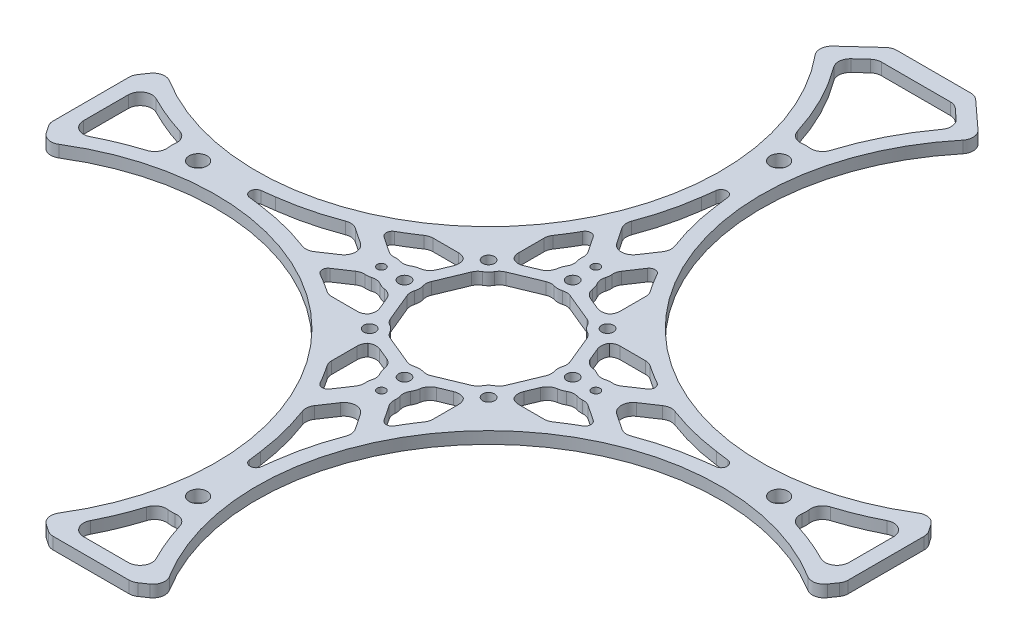
SolidWorks part; units mm, degrees
ref_plane "前视基准面" through (0, 0, 0) normal (0, 0, 1) x (1, 0, 0)
ref_plane "上视基准面" through (0, 0, 0) normal (0, 1, 0) x (1, 0, 0)
ref_plane "右视基准面" through (0, 0, 0) normal (1, 0, 0) x (0, 0, -1)
sketch "草图1" plane through (0, 0, 0) normal (0, 1, 0) x (1, 0, 0)
  line L113 (46.853, 0) -> (37.0698, -1.2734)
  line L116 (0, 46.853) -> (1.2734, 37.0698)
  line L147 (66.853, -7) -> (64.5647, -10.3188)
  line L164 (1.2737, 11.9909) -> (7.5782, 9.3795)
  line L244 (-0.0001, 20.7284) -> (4.0117, 26.7237)
  line L245 (5.4809, 23.5246) -> (2.3589, 18.8592)
  line L246 (7.4585, 11.5939) -> (2.9242, 13.4721)
  line L247 (8.5216, 12.6104) -> (8.5216, 18.495)
  line L253 (11.9909, -1.2737) -> (9.3795, -7.5782)
  line L254 (20.7284, 0.0001) -> (26.7237, -4.0117)
  line L257 (-8.5216, 12.6104) -> (-8.5216, 18.495)
  line L258 (-7.4585, 11.5939) -> (-2.9242, 13.4721)
  line L259 (-5.4809, 23.5246) -> (-2.3589, 18.8592)
  line L260 (0.0001, 20.7284) -> (-4.0117, 26.7237)
  line L262 (-1.2737, 11.9909) -> (-7.5782, 9.3795)
  line L266 (0, 46.853) -> (-1.2734, 37.0698)
  line L267 (23.5246, -5.4809) -> (18.8592, -2.3589)
  line L268 (11.5939, -7.4585) -> (13.4721, -2.9242)
  line L269 (12.6104, -8.5216) -> (18.495, -8.5216)
  line L272 (64.353, 7.1919) -> (64.353, -7.1919)
  line L273 (12.6104, 8.5216) -> (18.495, 8.5216)
  line L274 (11.5939, 7.4585) -> (13.4721, 2.9242)
  line L275 (23.5246, 5.4809) -> (18.8592, 2.3589)
  line L276 (20.7284, -0.0001) -> (26.7237, 4.0117)
  line L277 (11.9909, 1.2737) -> (9.3795, 7.5782)
  line L278 (66.853, 7) -> (64.5647, 10.3188)
  line L279 (66.853, -7) -> (66.853, 7)
  line L280 (46.853, 0) -> (37.0698, 1.2734)
  line L281 (0, -46.853) -> (-1.2734, -37.0698)
  line L282 (7, -66.853) -> (-7, -66.853)
  line L283 (-7, -66.853) -> (-10.3188, -64.5647)
  line L284 (-1.2737, -11.9909) -> (-7.5782, -9.3795)
  line L285 (0.0001, -20.7284) -> (-4.0117, -26.7237)
  line L286 (-5.4809, -23.5246) -> (-2.3589, -18.8592)
  line L287 (-7.4585, -11.5939) -> (-2.9242, -13.4721)
  line L288 (-8.5216, -12.6104) -> (-8.5216, -18.495)
  line L289 (-7.1919, -64.353) -> (7.1919, -64.353)
  line L290 (8.5216, -12.6104) -> (8.5216, -18.495)
  line L291 (7.4585, -11.5939) -> (2.9242, -13.4721)
  line L292 (5.4809, -23.5246) -> (2.3589, -18.8592)
  line L293 (-46.853, 0) -> (-37.0698, 1.2734)
  line L294 (-66.853, 7) -> (-64.5647, 10.3188)
  line L295 (-11.9909, 1.2737) -> (-9.3795, 7.5782)
  line L296 (-20.7284, -0.0001) -> (-26.7237, 4.0117)
  line L297 (-23.5246, 5.4809) -> (-18.8592, 2.3589)
  line L298 (-11.5939, 7.4585) -> (-13.4721, 2.9242)
  line L299 (-12.6104, 8.5216) -> (-18.495, 8.5216)
  line L300 (-0.0001, -20.7284) -> (4.0117, -26.7237)
  line L301 (1.2737, -11.9909) -> (7.5782, -9.3795)
  line L302 (-64.353, -7.1919) -> (-64.353, 7.1919)
  line L303 (-12.6104, -8.5216) -> (-18.495, -8.5216)
  line L304 (-11.5939, -7.4585) -> (-13.4721, -2.9242)
  line L305 (-23.5246, -5.4809) -> (-18.8592, -2.3589)
  line L306 (-20.7284, 0.0001) -> (-26.7237, -4.0117)
  line L307 (-11.9909, -1.2737) -> (-9.3795, -7.5782)
  line L308 (7, -66.853) -> (10.3188, -64.5647)
  line L309 (-66.853, -7) -> (-64.5647, -10.3188)
  line L310 (-66.853, 7) -> (-66.853, -7)
  line L311 (-46.853, 0) -> (-37.0698, -1.2734)
  line L312 (0, -46.853) -> (1.2734, -37.0698)
  line L314 (-7, 74.853) -> (7, 74.853)
  line L318 (7, 74.853) -> (13.6583, 68.7585)
  line L319 (0, -77.9383) -> (0, 77.9383) construction
  line L320 (-10.1817, 68.5516) -> (-6.5748, 71.853)
  line L322 (6.5748, 71.853) -> (-6.5748, 71.853)
  line L323 (10.1817, 68.5516) -> (6.5748, 71.853)
  line L324 (-7, 74.853) -> (-13.6583, 68.7585)
  circle A77 centre (0, 48.853) radius 1.5
  circle A138 centre (10, 10) radius 1
  circle A139 centre (0, 14.1421) radius 1
  circle A140 centre (0, 18.0312) radius 0.7
  arc A141 (-1.2737, 11.9909) -> (1.2737, 11.9909) centre (0, 14.1421) ccw
  arc A144 (7.5782, 9.3795) -> (9.3795, 7.5782) centre (10, 10) ccw
  arc A231 (4.0117, 26.7237) -> (1.2734, 37.0698) centre (42.4263, 42.4264) cw
  arc A232 (1.9284, 16.4402) -> (2.3589, 18.8592) centre (0, 18.0312) ccw
  arc A233 (2.9242, 13.4721) -> (1.9284, 16.4402) centre (0, 14.1421) ccw
  arc A234 (8.5216, 12.6104) -> (7.4585, 11.5939) centre (10, 10) ccw
  arc A235 (8.5216, 18.495) -> (5.4809, 23.5246) centre (42.4264, 42.4264) cw
  arc A236 (2.2334, 52.7597) -> (-2.2334, 52.7597) centre (0, 48.853) ccw
  arc A241 (-8.5216, 18.495) -> (-5.4809, 23.5246) centre (-42.4264, 42.4264) ccw
  arc A242 (-8.5216, 12.6104) -> (-7.4585, 11.5939) centre (-10, 10) cw
  arc A243 (-2.9242, 13.4721) -> (-1.9284, 16.4402) centre (0, 14.1421) cw
  arc A244 (-1.9284, 16.4402) -> (-2.3589, 18.8592) centre (0, 18.0312) cw
  arc A245 (-4.0117, 26.7237) -> (-1.2734, 37.0698) centre (-42.4263, 42.4264) ccw
  arc A246 (-7.5782, 9.3795) -> (-9.3795, 7.5782) centre (-10, 10) cw
  circle A247 centre (-10, 10) radius 1
  arc A249 (10.3188, -64.5647) -> (64.5647, -10.3188) centre (42.4264, -42.4264) cw
  circle A250 centre (10, -10) radius 1
  arc A251 (9.3795, -7.5782) -> (7.5782, -9.3795) centre (10, -10) ccw
  arc A252 (26.7237, -4.0117) -> (37.0698, -1.2734) centre (42.4264, -42.4263) cw
  arc A253 (16.4402, -1.9284) -> (18.8592, -2.3589) centre (18.0312, 0) ccw
  arc A254 (13.4721, -2.9242) -> (16.4402, -1.9284) centre (14.1421, 0) ccw
  arc A255 (12.6104, -8.5216) -> (11.5939, -7.4585) centre (10, -10) ccw
  arc A256 (18.495, -8.5216) -> (23.5246, -5.4809) centre (42.4264, -42.4264) cw
  arc A257 (52.7597, -2.2334) -> (64.353, -7.1919) centre (42.4264, -42.4264) cw
  arc A258 (52.7597, 2.2334) -> (64.353, 7.1919) centre (42.4264, 42.4264) ccw
  arc A259 (52.7597, 2.2334) -> (52.7597, -2.2334) centre (48.853, 0) cw
  arc A260 (18.495, 8.5216) -> (23.5246, 5.4809) centre (42.4264, 42.4264) ccw
  arc A261 (12.6104, 8.5216) -> (11.5939, 7.4585) centre (10, 10) cw
  arc A262 (13.4721, 2.9242) -> (16.4402, 1.9284) centre (14.1421, 0) cw
  arc A263 (16.4402, 1.9284) -> (18.8592, 2.3589) centre (18.0312, 0) cw
  arc A264 (26.7237, 4.0117) -> (37.0698, 1.2734) centre (42.4264, 42.4263) ccw
  arc A265 (11.9909, -1.2737) -> (11.9909, 1.2737) centre (14.1421, 0) cw
  circle A266 centre (18.0312, 0) radius 0.7
  circle A267 centre (14.1421, 0) radius 1
  circle A268 centre (48.853, 0) radius 1.5
  circle A269 centre (0, -48.853) radius 1.5
  circle A270 centre (0, -14.1421) radius 1
  circle A271 centre (0, -18.0312) radius 0.7
  arc A272 (1.2737, -11.9909) -> (-1.2737, -11.9909) centre (0, -14.1421) ccw
  arc A273 (-4.0117, -26.7237) -> (-1.2734, -37.0698) centre (-42.4263, -42.4264) cw
  arc A274 (-1.9284, -16.4402) -> (-2.3589, -18.8592) centre (0, -18.0312) ccw
  arc A275 (-2.9242, -13.4721) -> (-1.9284, -16.4402) centre (0, -14.1421) ccw
  arc A276 (-8.5216, -12.6104) -> (-7.4585, -11.5939) centre (-10, -10) ccw
  arc A277 (-8.5216, -18.495) -> (-5.4809, -23.5246) centre (-42.4264, -42.4264) cw
  arc A278 (-2.2334, -52.7597) -> (2.2334, -52.7597) centre (0, -48.853) ccw
  arc A279 (-2.2334, -52.7597) -> (-7.1919, -64.353) centre (-42.4264, -42.4264) cw
  arc A280 (2.2334, -52.7597) -> (7.1919, -64.353) centre (42.4264, -42.4264) ccw
  arc A281 (8.5216, -18.495) -> (5.4809, -23.5246) centre (42.4264, -42.4264) ccw
  arc A282 (8.5216, -12.6104) -> (7.4585, -11.5939) centre (10, -10) cw
  arc A283 (2.9242, -13.4721) -> (1.9284, -16.4402) centre (0, -14.1421) cw
  arc A284 (1.9284, -16.4402) -> (2.3589, -18.8592) centre (0, -18.0312) cw
  arc A285 (4.0117, -26.7237) -> (1.2734, -37.0698) centre (42.4263, -42.4264) ccw
  arc A286 (-26.7237, 4.0117) -> (-37.0698, 1.2734) centre (-42.4264, 42.4263) cw
  arc A287 (-16.4402, 1.9284) -> (-18.8592, 2.3589) centre (-18.0312, 0) ccw
  arc A288 (-13.4721, 2.9242) -> (-16.4402, 1.9284) centre (-14.1421, 0) ccw
  arc A289 (-12.6104, 8.5216) -> (-11.5939, 7.4585) centre (-10, 10) ccw
  arc A290 (-18.495, 8.5216) -> (-23.5246, 5.4809) centre (-42.4264, 42.4264) cw
  arc A291 (-52.7597, 2.2334) -> (-64.353, 7.1919) centre (-42.4264, 42.4264) cw
  arc A292 (-52.7597, -2.2334) -> (-64.353, -7.1919) centre (-42.4264, -42.4264) ccw
  arc A293 (-52.7597, -2.2334) -> (-52.7597, 2.2334) centre (-48.853, 0) cw
  arc A294 (-18.495, -8.5216) -> (-23.5246, -5.4809) centre (-42.4264, -42.4264) ccw
  arc A295 (-12.6104, -8.5216) -> (-11.5939, -7.4585) centre (-10, -10) cw
  arc A296 (-13.4721, -2.9242) -> (-16.4402, -1.9284) centre (-14.1421, 0) cw
  arc A297 (-16.4402, -1.9284) -> (-18.8592, -2.3589) centre (-18.0312, 0) cw
  arc A298 (-26.7237, -4.0117) -> (-37.0698, -1.2734) centre (-42.4264, -42.4263) ccw
  arc A299 (-9.3795, -7.5782) -> (-7.5782, -9.3795) centre (-10, -10) cw
  arc A300 (-11.9909, 1.2737) -> (-11.9909, -1.2737) centre (-14.1421, 0) cw
  circle A301 centre (-18.0312, 0) radius 0.7
  circle A302 centre (-14.1421, 0) radius 1
  circle A303 centre (-10, -10) radius 1
  arc A304 (-10.3188, -64.5647) -> (-64.5647, -10.3188) centre (-42.4264, -42.4264) ccw
  circle A305 centre (-48.853, 0) radius 1.5
  arc A306 (64.5647, 10.3188) -> (13.6583, 68.7585) centre (42.4264, 42.4263) cw
  arc A307 (2.2334, 52.7597) -> (10.1817, 68.5516) centre (42.4263, 42.4264) cw
  arc A308 (-2.2334, 52.7597) -> (-10.1817, 68.5516) centre (-42.4263, 42.4264) ccw
  arc A309 (-64.5647, 10.3188) -> (-13.6583, 68.7585) centre (-42.4264, 42.4263) ccw
  point P88 (64.853, 3.1887)
  point P89 (64.853, -3.1887)
  point P176 (-64.853, -3.1887)
  point P177 (3.1887, -64.853)
  point P178 (-3.1887, -64.853)
  point P179 (-64.853, 3.1887)
  point P189 (3.1887, 64.853)
extrude "凸台-拉伸1" add sketch "草图1" along normal blind 2 contours A77 region at (64.1049, 0, 7.5535)
fillet "圆角1" radius 2 94 edges at (7.5782, 1, -9.3795) (1.2737, 1, -11.9909) (4.0117, 1, -26.7237) (2.3589, 1, -18.8592) (1.9284, 1, -16.4402) (2.9242, 1, -13.4721) (7.4585, 1, -11.5939) (8.5216, 1, -12.6104) (8.5216, 1, -18.495) (-2.2334, 1, 52.7597) (-7.1919, 1, 64.353) (7.1919, 1, 64.353) (2.2334, 1, 52.7597) (18.8592, 1, -2.3589) (12.6104, 1, -8.5216) (11.5939, 1, -7.4585) (13.4721, 1, -2.9242) (16.4402, 1, -1.9284) (52.7597, 1, 2.2334) (64.353, 1, 7.1919) (64.353, 1, -7.1919) (52.7597, 1, -2.2334) (18.8592, 1, 2.3589) (16.4402, 1, 1.9284) (13.4721, 1, 2.9242) (11.5939, 1, 7.4585) (12.6104, 1, 8.5216) (18.495, 1, 8.5216) (-2.3589, 1, -18.8592) (-8.5216, 1, -18.495) (-8.5216, 1, -12.6104) (-7.4585, 1, -11.5939) (-2.9242, 1, -13.4721) (-1.9284, 1, -16.4402) (-2.3589, 1, 18.8592) (-1.9284, 1, 16.4402) (-2.9242, 1, 13.4721) (-7.4585, 1, 11.5939) (-8.5216, 1, 12.6104) (-8.5216, 1, 18.495) (2.3589, 1, 18.8592) (8.5216, 1, 18.495) (8.5216, 1, 12.6104) (7.4585, 1, 11.5939) (2.9242, 1, 13.4721) (1.9284, 1, 16.4402) (-18.8592, 1, -2.3589) (-16.4402, 1, -1.9284) (-13.4721, 1, -2.9242) (-11.5939, 1, -7.4585) (-12.6104, 1, -8.5216) (-18.495, 1, -8.5216) (-52.7597, 1, -2.2334) (-64.353, 1, -7.1919) (-64.353, 1, 7.1919) (-52.7597, 1, 2.2334) (-18.8592, 1, 2.3589) (-18.495, 1, 8.5216) (-12.6104, 1, 8.5216) (-11.5939, 1, 7.4585) (-13.4721, 1, 2.9242) (-16.4402, 1, 1.9284) (-11.9909, 1, 1.2737) (-9.3795, 1, 7.5782) (-7.5782, 1, 9.3795) (-1.2737, 1, 11.9909) (1.2737, 1, 11.9909) (7.5782, 1, 9.3795) (9.3795, 1, 7.5782) (11.9909, 1, 1.2737) (11.9909, 1, -1.2737) (9.3795, 1, -7.5782) (-1.2737, 1, -11.9909) (-7.5782, 1, -9.3795) (-9.3795, 1, -7.5782) (-11.9909, 1, -1.2737) (-26.7237, 1, -4.0117) (-26.7237, 1, 4.0117) (-20.7286, 1, 0) (-4.0117, 1, 26.7237) (4.0117, 1, 26.7237) (0, 1, 20.7286) (-4.0117, 1, -26.7237) (0, 1, -20.7286) (26.7237, 1, 4.0117) (26.7237, 1, -4.0117) (20.7286, 1, 0) (18.495, 1, -8.5216) (2.2334, 1, -52.7597) (6.5748, 1, -71.853) (-6.5748, 1, -71.853) (-10.1817, 1, -68.5516) (10.1817, 1, -68.5516) (-2.2334, 1, -52.7597)
fillet "圆角2" radius 1 12 edges at (23.5246, 1, -5.4809) (23.5246, 1, 5.4809) (5.4809, 1, -23.5246) (-5.4809, 1, -23.5246) (-5.4809, 1, 23.5246) (5.4809, 1, 23.5246) (-23.5246, 1, -5.4809) (-23.5246, 1, 5.4809) (0, 1, 46.853) (0, 1, -46.853) (46.853, 1, 0) (-46.853, 1, 0)
fillet "圆角3" radius 2 16 edges at (-13.6583, 1, -68.7585) (-7, 1, -74.853) (7, 1, -74.853) (64.5647, 1, -10.3188) (66.853, 1, -7) (66.853, 1, 7) (64.5647, 1, 10.3188) (10.3188, 1, 64.5647) (7, 1, 66.853) (-7, 1, 66.853) (-10.3188, 1, 64.5647) (-64.5647, 1, 10.3188) (-66.853, 1, 7) (-66.853, 1, -7) (-64.5647, 1, -10.3188) (13.6583, 1, -68.7585)
